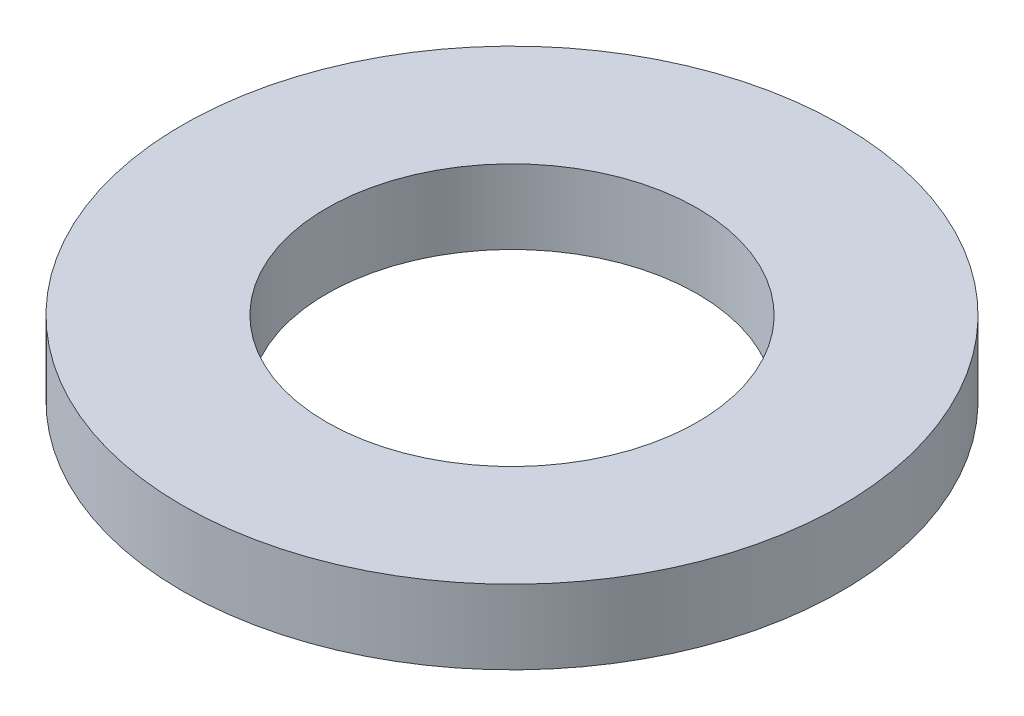
SolidWorks part; units mm, degrees
ref_plane "Front Plane" through (0, 0, 0) normal (0, 0, 1) x (1, 0, 0)
ref_plane "Top Plane" through (0, 0, 0) normal (0, 1, 0) x (1, 0, 0)
ref_plane "Right Plane" through (0, 0, 0) normal (1, 0, 0) x (0, 0, -1)
sketch "Sketch1" plane through (0, 0, 0) normal (0, 1, 0) x (1, 0, 0)
  circle A0 centre (0, 0) radius 80
  dimension "FLANGE_OD" = 160
extrude "Boss-Extrude1" add sketch "Sketch1" along normal blind 18
sketch "Sketch2" plane through (0, 0, 0) normal (0, 1, 0) x (1, 0, 0)
  circle A0 centre (0, 0) radius 45
  dimension "BORE_D" = 90
extrude "Cut-Extrude1" cut sketch "Sketch2" along normal through all
sketch "Sketch3" plane through (0, 18, 0) normal (0, 1, 0) x (1, 0, 0)
  circle A0 centre (0, 0) radius 35.6947 construction
  circle A1 centre (-35.6947, 0) radius 4.38
  dimension "BOLT_D" = 8.76
  dimension "BOLT_PCD" = 71.3893
extrude "Cut-Extrude2" cut sketch "Sketch3" against normal blind 15.0258 rebuild error yes
pattern_circular "CirPattern1" count 6 over 360 rebuild error yes
